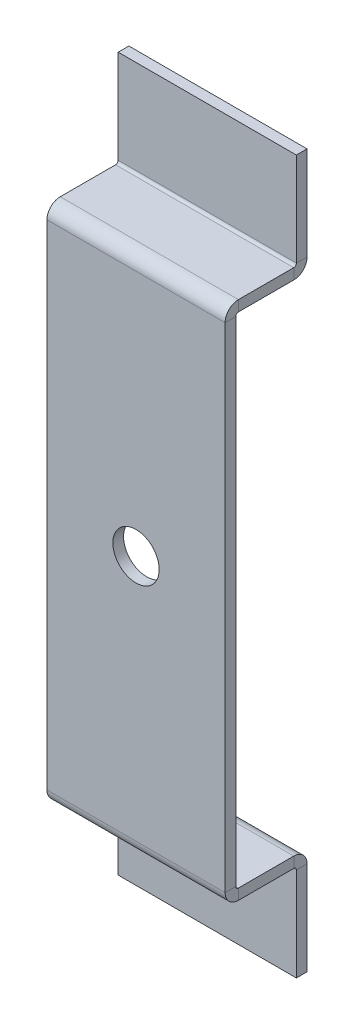
SolidWorks part; units mm, degrees
note: The reader was unsure of these and kept them because the rebuilt part matched: flange length of "边线-法兰1", "边线-法兰2".
ref_plane "前视基准面" through (0, 0, 0) normal (0, 0, 1) x (1, 0, 0)
ref_plane "上视基准面" through (0, 0, 0) normal (0, 1, 0) x (1, 0, 0)
ref_plane "右视基准面" through (0, 0, 0) normal (1, 0, 0) x (0, 0, -1)
other "Configuration Table"
sketch "草图1" plane through (0, 0, 0) normal (0, 0, 1) x (1, 0, 0)
  line L1 (0, 0) -> (50, 0)
  line L2 (0, 0) -> (0, 140)
  line L3 (0, 140) -> (50, 140)
  line L4 (50, 0) -> (50, 140)
  dimension "D1" = 140
  dimension "D2" = 50
base flange "基体-法兰1" sketch "草图1" thickness 3 reverse thickness direction no parameters "D1"=0.7366
edge flange "边线-法兰1" sketch "草图10" flange profiles "草图10", "草图11" flange angle 90 flange length 20 flange position material outside bend radius 0.7366 thickness 3 relief rectangular parameters "D6"=10, "D8"=1
sketch "草图10" plane through (0, 140, -3) normal (0, -1, 0) x (-1, 0, 0)
  line L2 (-50, 0) -> (-50, 17)
  line L3 (-50, 17) -> (0, 17)
  line L4 (0, 17) -> (0, 0)
  line L5 (0, 0) -> (-50, 0) construction
  line L6 (0, 0) -> (-50, 0)
sketch "草图11" plane through (0, 0, -3) normal (0, 1, 0) x (1, 0, 0)
  line L0 (50, 0) -> (0, 0) construction
  line L1 (50, 0) -> (0, 0)
  line L2 (50, 0) -> (50, 17)
  line L3 (50, 17) -> (0, 17)
  line L4 (0, 17) -> (0, 0)
bend "边线折弯1" bend radius 0.7366 bend angle 90 parameters "D5"=1
bend "边线折弯2" bend radius 0.7366 bend angle 90 parameters "D5"=2
edge flange "边线-法兰2" sketch "草图16" flange profiles "草图16", "草图17" flange angle 90 flange length 30 flange position material outside bend radius 0.7366 thickness 3 relief rectangular parameters "D6"=10, "D8"=1
sketch "草图16" plane through (0, -3, -20) normal (0, 0, -1) x (1, 0, 0)
  line L2 (0, 0) -> (0, 27)
  line L3 (0, 27) -> (50, 27)
  line L4 (50, 27) -> (50, 0)
  line L7 (50, 0) -> (0, 0) construction
  line L8 (50, 0) -> (0, 0)
sketch "草图17" plane through (0, 143, -20) normal (0, 0, -1) x (-1, 0, 0)
  line L0 (0, 0) -> (-50, 0) construction
  line L1 (0, 0) -> (-50, 0)
  line L2 (-50, 0) -> (-50, 27)
  line L3 (-50, 27) -> (0, 27)
  line L4 (0, 27) -> (0, 0)
bend "边线折弯3" bend radius 0.7366 bend angle 90 parameters "D5"=3
bend "边线折弯4" bend radius 0.7366 bend angle 90 parameters "D5"=4
sketch "草图18" plane through (0, 0, 0) normal (0, 0, 1) x (1, 0, 0)
  line L7 (50, -30) -> (0, -30) construction
  line L8 (50, 0.7366) -> (50, 139.2634) construction
  circle A0 centre (25, 70) radius 6.5
  dimension "D5" = 13
  dimension "D3" = 100
  dimension "D4" = 25
extrude "切除-拉伸1" cut sketch "草图18" against normal through all normal cut yes
sketch "折弯-线1" plane through (0, 0, 0) normal (0, 1, 0) x (1, 0, 0)
sketch "边界框1" plane through (0, 0, 0) normal (0, 1, 0) x (1, 0, 0)
sheet metal parameters "钣金6" thickness 3 parameters "D1"=0.7366
flat pattern "平板型式6" [suppressed]
sketch "折弯-线2" plane through (0, 0, 0) normal (0, 1, 0) x (1, 0, 0)
sketch "边界框2" [suppressed] plane through (0, 0, 0) normal (0, 1, 0) x (1, 0, 0)
sheet metal parameters "钣金7" thickness 3 parameters "D1"=0.7366
flat pattern "平板型式6" [suppressed]
sketch "折弯-线2" plane through (0, 0, 0) normal (0, 1, 0) x (1, 0, 0)
sketch "边界框2" [suppressed] plane through (0, 0, 0) normal (0, 1, 0) x (1, 0, 0)
bend of the flat pattern "展平-<边线折弯1>1"
bend of the flat pattern "展平-<边线折弯2>1"
sheet metal parameters "钣金8" thickness 3 parameters "D1"=0.7366
flat pattern "平板型式6" [suppressed]
sketch "折弯-线2" plane through (0, 0, 0) normal (0, 1, 0) x (1, 0, 0)
sketch "边界框2" [suppressed] plane through (0, 0, 0) normal (0, 1, 0) x (1, 0, 0)
bend of the flat pattern "展平-<边线折弯1>1"
bend of the flat pattern "展平-<边线折弯2>1"
bend of the flat pattern "展平-<边线折弯3>1"
bend of the flat pattern "展平-<边线折弯4>1"
sheet metal parameters "钣金9" thickness 3 parameters "D1"=0.7366
flat pattern "平板型式6" [suppressed]
sketch "折弯-线2" plane through (0, 0, 0) normal (0, 1, 0) x (1, 0, 0)
sketch "边界框2" [suppressed] plane through (0, 0, 0) normal (0, 1, 0) x (1, 0, 0)
bend of the flat pattern "展平-<边线折弯1>1"
bend of the flat pattern "展平-<边线折弯2>1"
bend of the flat pattern "展平-<边线折弯3>1"
bend of the flat pattern "展平-<边线折弯4>1"
